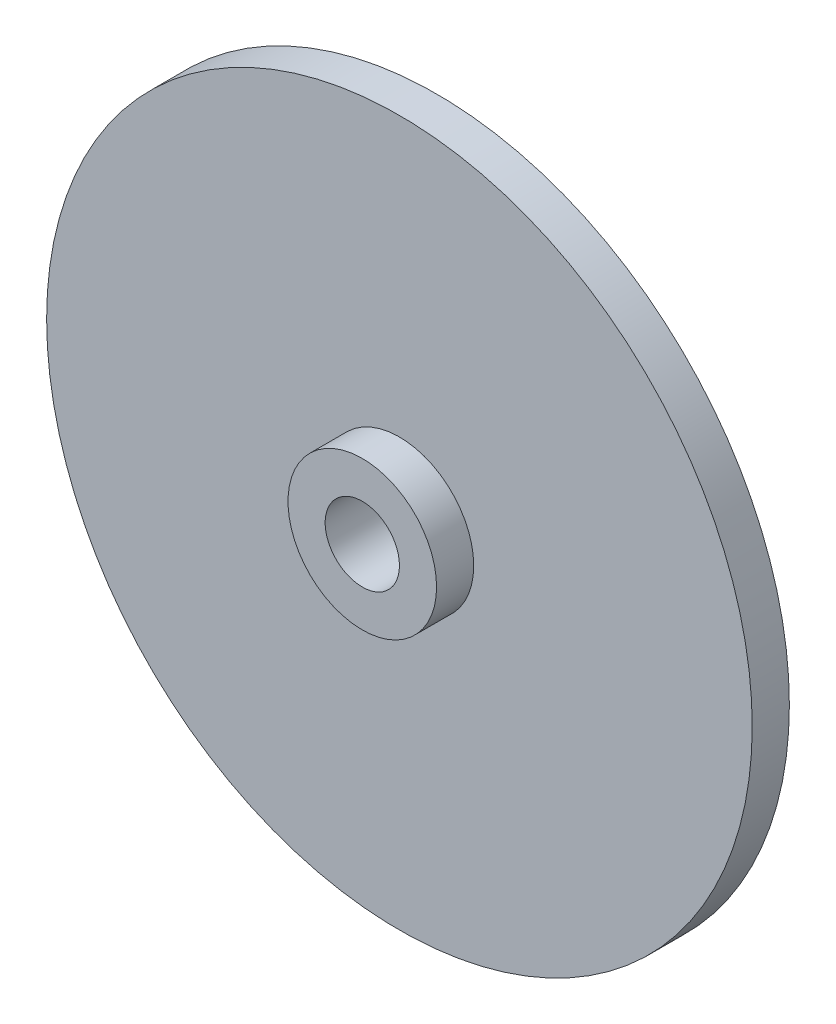
SolidWorks part; units mm, degrees
ref_plane "Front Plane" through (0, 0, 0) normal (0, 0, 1) x (1, 0, 0)
ref_plane "Top Plane" through (0, 0, 0) normal (0, 1, 0) x (1, 0, 0)
ref_plane "Right Plane" through (0, 0, 0) normal (1, 0, 0) x (0, 0, -1)
sketch "Sketch1" plane through (0, 0, 0) normal (0, 0, 1) x (1, 0, 0)
  circle A0 centre (0, 0) radius 9.5
  circle A1 centre (0, 0) radius 2
  circle A2 centre (0, 0) radius 1
extrude "Boss-Extrude1" add sketch "Sketch1" along normal blind 1 contours A0 A1 region at (-9.2313, 0, 0)
extrude "Boss-Extrude2" add sketch "Sketch1<3>" along normal blind 2 contours A1 A2 region at (-1.9434, 0, 0)
sketch "Sketch1<3>" plane through (0, 0, 0) normal (0, 0, 1) x (1, 0, 0) same geometry as "Sketch1"
